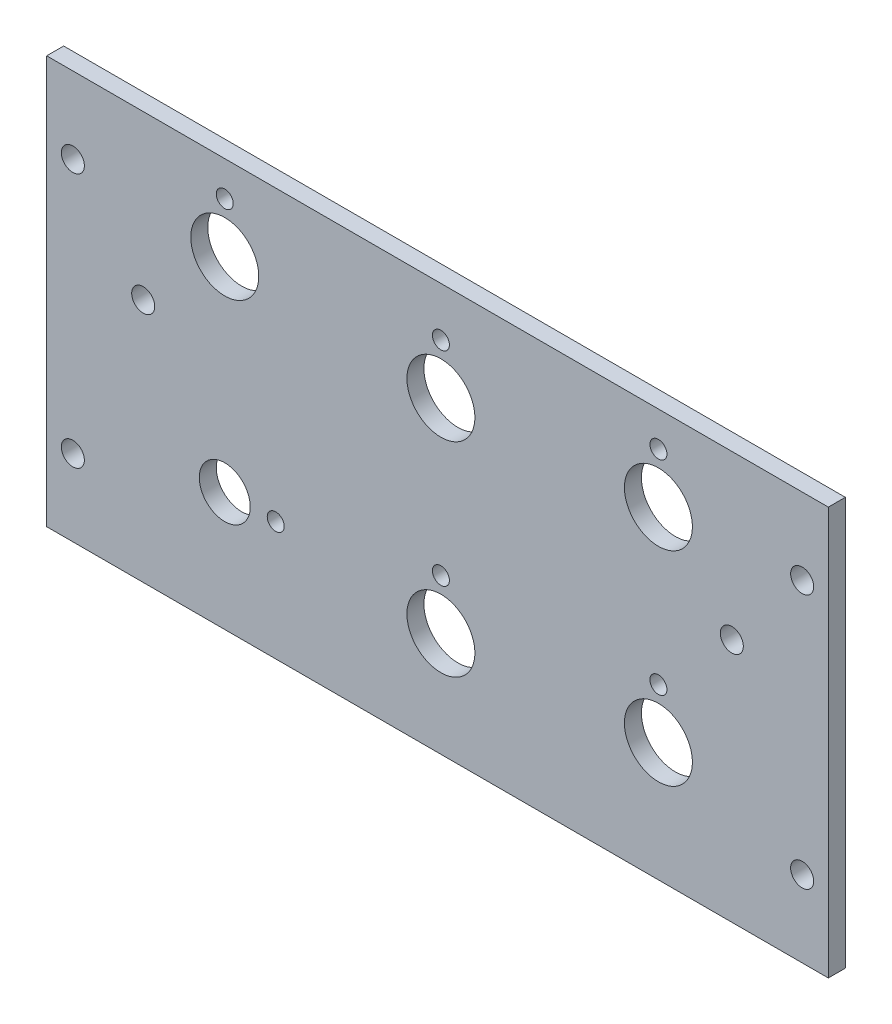
SolidWorks part; units mm, degrees
ref_plane "Front Plane" through (0, 0, 0) normal (0, 0, 1) x (1, 0, 0)
ref_plane "Top Plane" through (0, 0, 0) normal (0, 1, 0) x (1, 0, 0)
ref_plane "Right Plane" through (0, 0, 0) normal (1, 0, 0) x (0, 0, -1)
sketch "Sketch1" plane through (0, 0, 0) normal (0, 0, 1) x (1, 0, 0)
  line L4 (0, 76.2) -> (-146.05, 76.2)
  line L5 (-146.05, 76.2) -> (-146.05, 0)
  line L6 (-146.05, 0) -> (0, 0)
  line L7 (0, 0) -> (0, 76.2)
  line L8 (0, 76.2) -> (-146.05, 76.2)
  line L9 (-146.05, 76.2) -> (-146.05, 0)
  line L10 (-146.05, 0) -> (0, 0)
  line L11 (0, 0) -> (0, 76.2)
  dimension "D1" = 0
extrude "Boss-Extrude1" add sketch "Sketch1" against normal blind 3.175
hole_wizard "#6 Clearance Hole1" positions "Sketch3" profile "Sketch2" hole size "#6" standard "ANSI Inch" end condition through all
sketch "Sketch3" plane through (0, 0, -3.175) normal (0, 0, -1) x (-1, 0, 0)
  point P0 (4.8895, 61.9125)
  point P3 (4.8895, 14.2875)
  point P6 (141.1605, 14.2875)
  point P9 (141.1605, 61.9125)
  point P12 (128.016, 45.72)
  point P15 (18.034, 45.72)
sketch "Sketch2" plane through (-4.8895, 61.9125, -3.175) normal (1, 0, 0) x (0, 1, 0)
  line L0 (0, 0) -> (0, 3.175)
  line L1 (0, 3.175) -> (2.1526, 3.175)
  line L2 (2.1526, 3.175) -> (2.1526, 0)
  line L5 (2.1526, 0) -> (0, 0)
  line L11 (0, -6.35) -> (0, 107.95) construction
  dimension "Thru Hole Dia." = 4.3053
  dimension "Thru Hole Depth" = 3.175
hole_wizard "3/8 (0.375) Diameter Hole1" positions "Sketch7" profile "Sketch6" hole size "3/8" standard "ANSI Inch" end condition through all
sketch "Sketch7" plane through (0, 0, -3.175) normal (0, 0, -1) x (-1, 0, 0)
  line L0 (0, 0) -> (0, 76.2) construction
  line L1 (0, 76.2) -> (146.05, 76.2) construction
  point P3 (112.776, 22.225)
  dimension "D1" = 112.776
  dimension "D2" = 53.975
sketch "Sketch6" plane through (-112.776, 22.225, -3.175) normal (1, 0, 0) x (0, 1, 0)
  line L0 (0, 0) -> (0, 3.175)
  line L1 (0, 3.175) -> (4.7625, 3.175)
  line L2 (4.7625, 3.175) -> (4.7625, 0)
  line L5 (4.7625, 0) -> (0, 0)
  line L11 (0, -6.35) -> (0, 107.95) construction
  dimension "Thru Hole Dia." = 9.525
  dimension "Thru Hole Depth" = 3.175
hole_wizard "1/2 (0.5) Diameter Hole1" positions "Sketch5" profile "Sketch4" hole size "1/2" standard "ANSI Inch" end condition through all
sketch "Sketch5" plane through (0, 0, -3.175) normal (0, 0, -1) x (-1, 0, 0)
  line L0 (0, 0) -> (0, 76.2) construction
  line L1 (0, 76.2) -> (146.05, 76.2) construction
  line L2 (0, 38.1) -> (146.05, 38.1) construction
  line L3 (146.05, 76.2) -> (146.05, 0) construction
  line L5 (112.776, 22.225) -> (31.75, 22.225) construction
  point P0 (31.75, 60.325)
  point P3 (72.39, 57.658)
  point P6 (112.776, 60.325)
  point P29 (31.75, 22.225)
  point P30 (72.39, 19.558)
  dimension "D1" = 31.75
  dimension "D2" = 15.875
  dimension "D3" = 2.667
  dimension "D4" = 40.64
  dimension "D5" = 81.026
  dimension "D6" = 2.667
sketch "Sketch4" plane through (-31.75, 60.325, -3.175) normal (1, 0, 0) x (0, 1, 0)
  line L0 (0, 0) -> (0, 3.175)
  line L1 (0, 3.175) -> (6.35, 3.175)
  line L2 (6.35, 3.175) -> (6.35, 0)
  line L5 (6.35, 0) -> (0, 0)
  line L11 (0, -6.35) -> (0, 107.95) construction
  dimension "Thru Hole Dia." = 12.7
  dimension "Thru Hole Depth" = 3.175
hole_wizard "1/8 (0.125) Diameter Hole1" positions "Sketch9" profile "Sketch8" hole size "1/8" standard "ANSI Inch" end condition through all
sketch "Sketch9" plane through (0, 0, -3.175) normal (0, 0, -1) x (-1, 0, 0)
  line L0 (31.75, 69.6995) -> (31.75, 60.325) construction
  line L2 (72.39, 57.658) -> (72.39, 67.0325) construction
  line L4 (112.776, 60.325) -> (112.776, 69.6995) construction
  line L6 (31.75, 22.225) -> (31.75, 31.5995) construction
  line L8 (72.39, 19.558) -> (72.39, 28.9325) construction
  point P0 (31.75, 69.6995)
  point P2 (112.776, 69.6995)
  point P4 (103.251, 22.225)
  point P14 (72.39, 67.0325)
  point P23 (31.75, 31.5995)
  point P27 (72.39, 28.9325)
  dimension "D1" = 9.3745
sketch "Sketch8" plane through (-31.75, 69.6995, -3.175) normal (1, 0, 0) x (0, 1, 0)
  line L0 (0, 0) -> (0, 3.175)
  line L1 (0, 3.175) -> (1.5875, 3.175)
  line L2 (1.5875, 3.175) -> (1.5875, 0)
  line L5 (1.5875, 0) -> (0, 0)
  line L11 (0, -6.35) -> (0, 107.95) construction
  dimension "Thru Hole Dia." = 3.175
  dimension "Thru Hole Depth" = 3.175
equation "\"D6@Sketch5\"=\"D3@Sketch5\""
